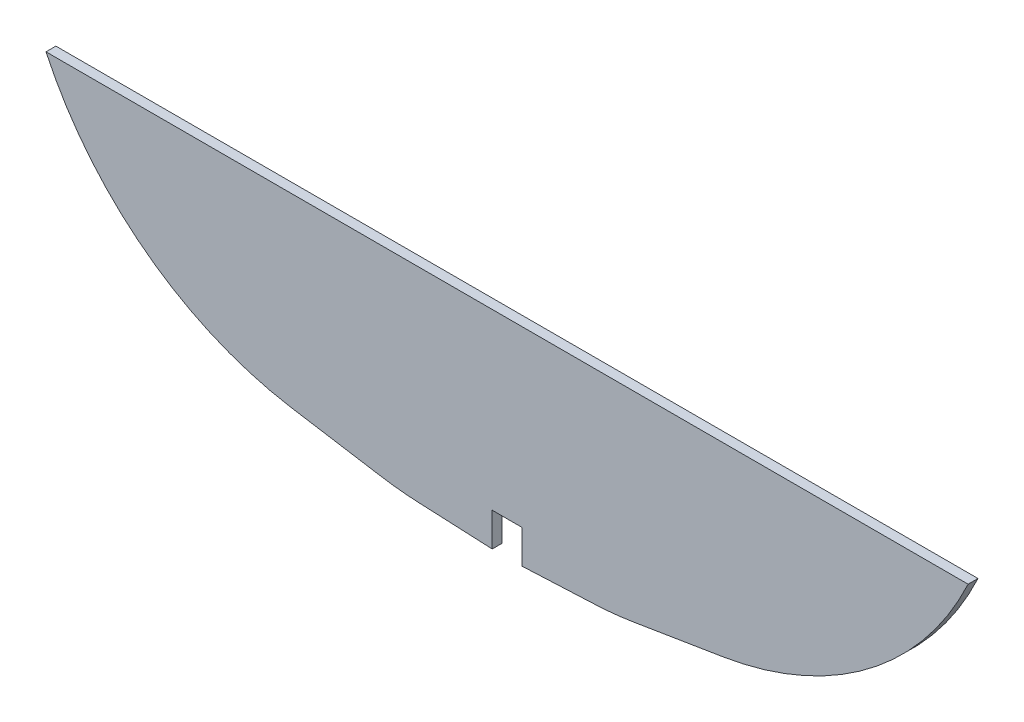
SolidWorks part; units mm, degrees
ref_plane "Plan de face" through (0, 0, 0) normal (0, 0, 1) x (1, 0, 0)
ref_plane "Plan de dessus" through (0, 0, 0) normal (0, 1, 0) x (1, 0, 0)
ref_plane "Plan de droite" through (0, 0, 0) normal (1, 0, 0) x (0, 0, -1)
sketch "Esquisse1" plane through (0, 0, 0) normal (0, 0, 1) x (1, 0, 0)
  line L0 (-103.9234, 35.4316) -> (176.0766, 35.4316)
  line L1 (-103.9234, 35.4316) -> (-93.9997, -10.3765)
  line L3 (31.5766, -27.5684) -> (31.5766, -17.3684)
  line L4 (31.5766, -17.3684) -> (40.5766, -17.3684)
  line L5 (36.0766, 35.4316) -> (36.0766, -17.3684) construction
  line L6 (40.5766, -27.5684) -> (40.5766, -17.3684)
  line L8 (176.0766, 35.4316) -> (166.1528, -10.3765)
  line L9 (31.5766, -27.5684) -> (3.4312, -26.2574)
  line L10 (3.4312, -26.2574) -> (-93.9997, -10.3765)
  line L11 (40.5766, -27.5684) -> (68.722, -26.2574)
  line L12 (68.722, -26.2574) -> (166.1528, -10.3765)
  point P11 (68.722, -26.2574)
  point P13 (189.78, -5.0881)
  point P14 (182.5047, -9.5568)
  point P15 (0, 0)
  point P16 (-93.9997, -10.3765)
  dimension "D1" = 140
  dimension "D4" = 9
  dimension "D5" = 10.2
  dimension "D6" = 52.8
extrude "Boss.-Extru.1" add sketch "Esquisse1" along normal blind 3
fillet "Congé1" radius 100 4 edges at (166.1528, -10.3765, 1.5) (68.722, -26.2574, 1.5) (3.4312, -26.2574, 1.5) (-93.9997, -10.3765, 1.5)
